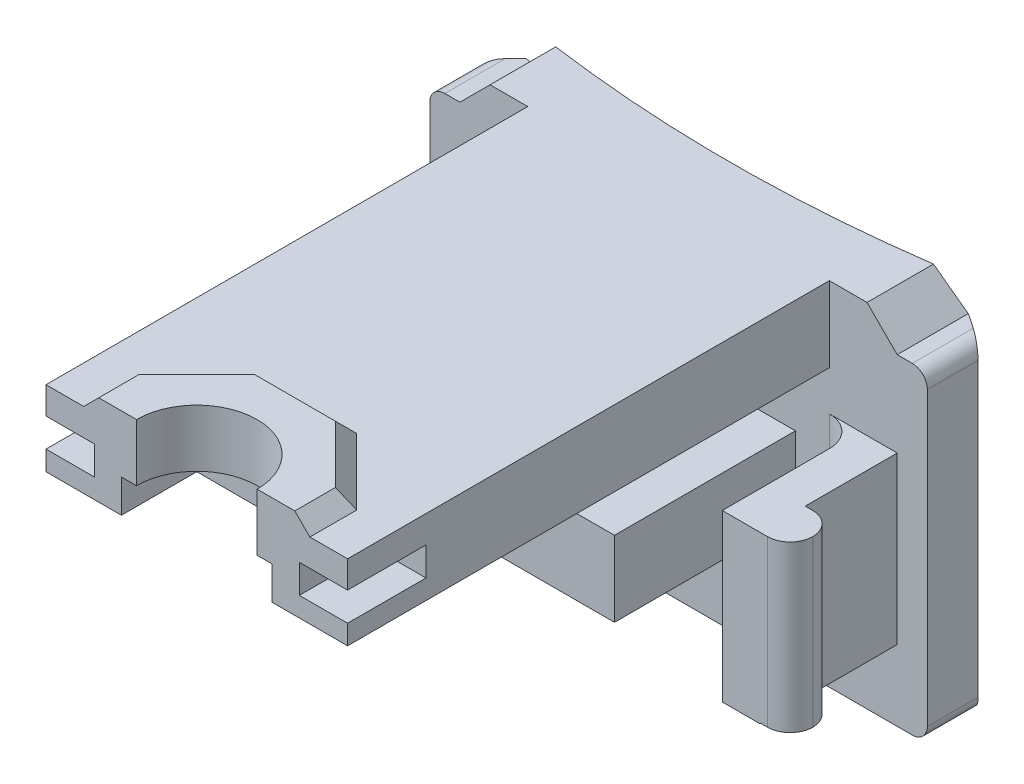
SolidWorks part; units mm, degrees
ref_plane "Front Plane" through (0, 0, 0) normal (0, 0, 1) x (1, 0, 0)
ref_plane "Top Plane" through (0, 0, 0) normal (0, 1, 0) x (1, 0, 0)
ref_plane "Right Plane" through (0, 0, 0) normal (1, 0, 0) x (0, 0, -1)
sketch "Sketch1" plane through (0, 0, 0) normal (0, 0, 1) x (1, 0, 0)
  line L0 (-16.5, 10.675) -> (-14.5, 10.675)
  line L1 (-16.5, 10.675) -> (-14.5, 10.675)
  line L2 (-16.5, 10.675) -> (-16.5, -10.675)
  line L3 (-16.5, -10.675) -> (16.5, -10.675)
  line L4 (16.5, 10.675) -> (16.5, -10.675)
  line L5 (16.5, 10.675) -> (14.5, 10.675)
  line L6 (14.5, 10.675) -> (14.5, 12.675)
  line L7 (14.5, 12.675) -> (-14.5, 12.675)
  line L8 (-14.5, 12.675) -> (-14.5, 10.675)
  line L9 (14.5, 10.675) -> (16.5, 10.675)
  point P0 (0, 0)
  dimension "D1" = 21.35
  dimension "D2" = 33
  dimension "D3" = 2
  dimension "D4" = 2
  dimension "D5" = 2
extrude "Boss-Extrude1" add sketch "Sketch1" along normal blind 3 contours L7 L8 L0 L2 L3 L4 L5 L6
sketch "Sketch2" plane through (0, 0, 3) normal (0, 0, 1) x (1, 0, 0)
  line L0 (12, -5.875) -> (12, -5.975)
  line L1 (12, -5.975) -> (14.5, -5.975)
  line L2 (-14.5, -8.675) -> (-14.5, 7.675)
  line L4 (-14.5, -8.675) -> (14.5, -8.675)
  line L5 (14.5, -0.5) -> (14.5, -5.875)
  line L6 (12, 5.025) -> (14.5, 5.025)
  line L7 (14.5, -8.675) -> (14.5, 7.675)
  line L8 (14.5, 7.675) -> (-14.5, 7.675)
  line L10 (12, -0.375) -> (12, -5.875)
  line L12 (14.5, -0.5) -> (14.5, 5.3947)
  line L14 (12, -0.375) -> (12, 5.025)
  line L16 (-12, -0.6119) -> (-12, -5.975)
  line L17 (-12, -0.6119) -> (-12, 4.7416)
  line L18 (-12, 5.0127) -> (-14.5, 5.0114)
  line L19 (-14.5, -5.8422) -> (-14.5, -5.9422)
  line L22 (-14.5, 5.1114) -> (-14.5, 5.0114)
  line L23 (-12, 4.7416) -> (-12, 5.0127)
  line L24 (-12, -5.975) -> (-14.5, -5.975)
  dimension "D1" = 5.5
  dimension "D2" = 0.1
  dimension "D3" = 2.5
  dimension "D4" = 0.1
  dimension "D5" = 0.1
  dimension "D6" = 11
  dimension "D7" = 2.7
  dimension "D8" = 2.7
extrude "Boss-Extrude2" add sketch "Sketch2" along normal blind 9.1
sketch "Sketch3" plane through (-14.5, 0, 0) normal (-1, 0, 0) x (0, 0, 1)
  line L12 (12.1, -5.925) -> (3, -5.925) construction
  line L13 (12.1, 5.2947) -> (9.1, 5.2947)
  line L14 (12.1, 5.2947) -> (12.1, -5.925)
  line L15 (12.1, -5.925) -> (9.1, -5.925)
  line L16 (9.1, 5.2947) -> (9.1, -5.925)
  dimension "D1" = 3
extrude "Boss-Extrude3" add sketch "Sketch3" along normal blind 2
sketch "Sketch4" plane through (14.5, 0, 0) normal (1, 0, 0) x (0, 0, -1)
  line L15 (-12.1, 5.025) -> (-9.1, 5.025)
  line L16 (-12.1, 5.025) -> (-12.1, -5.925)
  line L17 (-12.1, -5.925) -> (-9.1, -5.925)
  line L18 (-9.1, 5.025) -> (-9.1, -5.925)
extrude "Boss-Extrude4" add sketch "Sketch4" along normal blind 2
fillet "Fillet2" radius 1.5 8 edges at (-16.5, -5.925, 10.6) (-16.5, 5.0114, 10.6) (-16.5, -0.4568, 9.1) (-16.5, -0.4568, 12.1) (16.5, -0.45, 9.1) (16.5, 5.025, 10.6) (16.5, -0.45, 12.1) (16.5, -5.925, 10.6)
fillet "Fillet3" radius 2 2 edges at (12, -0.475, 3) (-12, -0.4812, 3)
sketch "Sketch6" plane through (0, 12.675, 0) normal (0, 1, 0) x (1, 0, 0)
  line L1 (14.5, -3) -> (-14.5, -3) construction
  line L4 (10, -3) -> (-10, -3)
  line L5 (10, -3) -> (10, -34.95)
  line L6 (10, -34.95) -> (-10, -34.95)
  line L7 (-10, -3) -> (-10, -34.95)
  dimension "D3" = 31.95
extrude "Boss-Extrude5" add sketch "Sketch6" against normal blind 5
sketch "Sketch7" plane through (0, 12.675, 0) normal (0, 1, 0) x (1, 0, 0)
  line L0 (-10, -34.95) -> (10, -34.95) construction
  line L1 (-4, -34.95) -> (4, -34.95)
  arc A0 (4, -34.95) -> (-4, -34.95) centre (0, -34.95) ccw
  dimension "D1" = 8
extrude "Cut-Extrude1" cut sketch "Sketch7" against normal up to next
sketch "Sketch8" plane through (0, 12.675, 0) normal (0, 1, 0) x (1, 0, 0)
  line L0 (-7.5, -34.95) -> (-4, -34.95)
  line L1 (7.5, -34.95) -> (7.5, -31.8434)
  line L2 (7.5, -31.8434) -> (3.1066, -27.45)
  line L3 (3.1066, -27.45) -> (-3.1066, -27.45)
  line L4 (-3.1066, -27.45) -> (-7.5, -31.8434)
  line L5 (-7.5, -31.8434) -> (-7.5, -34.95)
  line L9 (4, -34.95) -> (7.5, -34.95)
  line L10 (-7.3949, -38.1617) -> (-3.0316, -42.525)
  line L11 (3.2117, -42.3449) -> (7.575, -37.9816)
  line L12 (-2.9579, -42.45) -> (3.2126, -42.45)
  arc A0 (-4, -34.95) -> (4, -34.95) centre (0, -34.95) cw
  arc A1 (4, -34.95) -> (-4, -34.95) centre (0, -34.95) ccw construction
  dimension "D1" = 15
extrude "Boss-Extrude6" add sketch "Sketch8" along normal blind 1
chamfer "Chamfer1" distance 1 angle 45 5 edges at (-7.5, 13.675, 33.3967) (-5.3033, 13.675, 29.6467) (0, 13.675, 27.45) (5.3033, 13.675, 29.6467) (7.5, 13.675, 33.3967)
sketch "Sketch10" plane through (0, 7.675, 0) normal (0, -1, 0) x (1, 0, 0)
  line L0 (-7.75, 3) -> (7.75, 3)
  line L2 (10, 3) -> (-10, 3) construction
  line L3 (7.75, 3) -> (7.75, 23)
  line L5 (-7.75, 3) -> (-7.75, 23)
  line L6 (-7.75, 23) -> (7.75, 23)
  dimension "D1" = 15.5
  dimension "D2" = 20
extrude "Boss-Extrude7" add sketch "Sketch10" along normal blind 1.75
sketch "Sketch11" plane through (0, 0, 3) normal (0, 0, 1) x (1, 0, 0)
  line L0 (-7.75, -2.075) -> (7.75, -2.075)
  line L1 (7.75, 1.425) -> (7.75, 2.925)
  line L3 (-7.75, -2.075) -> (-7.75, 1.425)
  line L8 (7.75, 1.425) -> (7.75, -2.075)
  line L9 (7.75, 1.425) -> (7.75, -2.075)
  line L10 (7.75, 5.925) -> (7.75, 2.925)
  line L11 (7.75, 2.925) -> (-7.75, 2.925)
  line L12 (-7.75, 2.925) -> (-7.75, -2.075)
  dimension "D1" = 1.5
  dimension "D2" = 3
  dimension "D3" = 5
extrude "Boss-Extrude8" add sketch "Sketch11" along normal blind 12
sketch "Sketch12" plane through (0, 12.675, 0) normal (0, 1, 0) x (1, 0, 0)
  line L0 (-16.5, 0) -> (-16.5, 2)
  line L1 (16.5, 0) -> (16.5, 2.0708)
  line L2 (-16.5, 0) -> (16.5, 0)
  arc A0 (-16.5, 2) -> (16.5, 2.0708) centre (-0.1897, 90.5097) ccw
  dimension "D2" = 90
  dimension "D1" = 2
extrude "Boss-Extrude9" add sketch "Sketch12" against normal through all
chamfer "Chamfer3" distance 2 angle 45 2 edges at (16.5, 1, -2.0708) (-16.5, 1, -2)
fillet "Fillet4" radius 1 4 edges at (16.5, -10.675, 1.3207) (-16.5, -10.675, 1.5) (16.5, 10.675, 1.5) (-16.5, 10.675, 1.5)
chamfer "Chamfer4" distance 2 angle 45 2 edges at (-14.5, 12.675, 1.5) (14.5, 12.675, 1.5)
sketch "Sketch13" plane through (0, 0, 0) normal (0, 0, 1) x (1, 0, 0)
  line L0 (12.5, 12.675) -> (16.5, 12.675)
  line L1 (12.5, 12.675) -> (14.5, 10.675) construction
  line L2 (12.5, 12.675) -> (16.5, 12.675) construction
  line L3 (16.5, 12.675) -> (16.5, 9.675)
  line L4 (16.5, 9.675) -> (16.5, 12.675) construction
  line L5 (14.5, 10.675) -> (12.5, 12.675)
  line L6 (-12.5, 12.675) -> (-16.5, 12.675)
  line L8 (-14.5, 10.675) -> (-12.5, 12.675)
  line L9 (-16.5, 12.675) -> (-16.5, 9.675)
  line L10 (-14.5, 10.675) -> (-15.5, 10.675)
  line L11 (14.5, 10.675) -> (15.5, 10.675)
  arc A0 (16.5, 9.675) -> (15.5, 10.675) centre (15.5, 9.675) ccw construction
  arc A5 (-15.5, 10.675) -> (-16.5, 9.675) centre (-15.5, 9.675) ccw
  arc A6 (15.5, 10.675) -> (16.5, 9.675) centre (15.5, 9.675) cw
extrude "Cut-Extrude2" cut sketch "Sketch13" against normal through all
sketch "Sketch14" plane through (10, 0, 0) normal (1, 0, 0) x (0, 0, -1)
  line L0 (-34.95, 10.875) -> (-34.95, 8.975)
  line L1 (-34.95, 7.675) -> (-34.95, 12.675) construction
  line L2 (-29.75, 10.675) -> (-29.75, 10.875)
  line L6 (-29.75, 10.675) -> (-29.75, 9.175)
  line L7 (-29.75, 9.175) -> (-29.75, 8.975)
  line L8 (-29.75, 10.875) -> (-34.95, 10.875)
  line L9 (-29.75, 8.975) -> (-34.95, 8.975)
  dimension "D1" = 5.2
  dimension "D2" = 1.5
  dimension "D4" = 0.2
  dimension "D5" = 0.2
extrude "Cut-Extrude3" cut sketch "Sketch14" against normal blind 3.2
sketch "Sketch15" plane through (-10, 0, 0) normal (-1, 0, 0) x (0, 0, 1)
  line L0 (29.75, 10.875) -> (29.75, 8.975)
  line L1 (34.95, 7.675) -> (34.95, 12.675) construction
  line L2 (34.95, 10.875) -> (34.95, 8.975)
  line L7 (34.95, 8.975) -> (29.75, 8.975)
  line L9 (29.75, 10.875) -> (34.95, 10.875)
  dimension "D1" = 5.2
extrude "Cut-Extrude4" cut sketch "Sketch15" against normal blind 3.2
sketch "Sketch16" plane through (0, 7.675, 0) normal (0, -1, 0) x (1, 0, 0)
  line L0 (-5, 34.95) -> (5, 34.95)
  line L2 (-5, 34.95) -> (-5, 29.95)
  line L3 (-5, 29.95) -> (5, 29.95)
  line L4 (5, 34.95) -> (5, 29.95)
  point P0 (0, 34.95)
  dimension "D2" = 10
extrude "Cut-Extrude5" cut sketch "Sketch16" against normal blind 2.2
